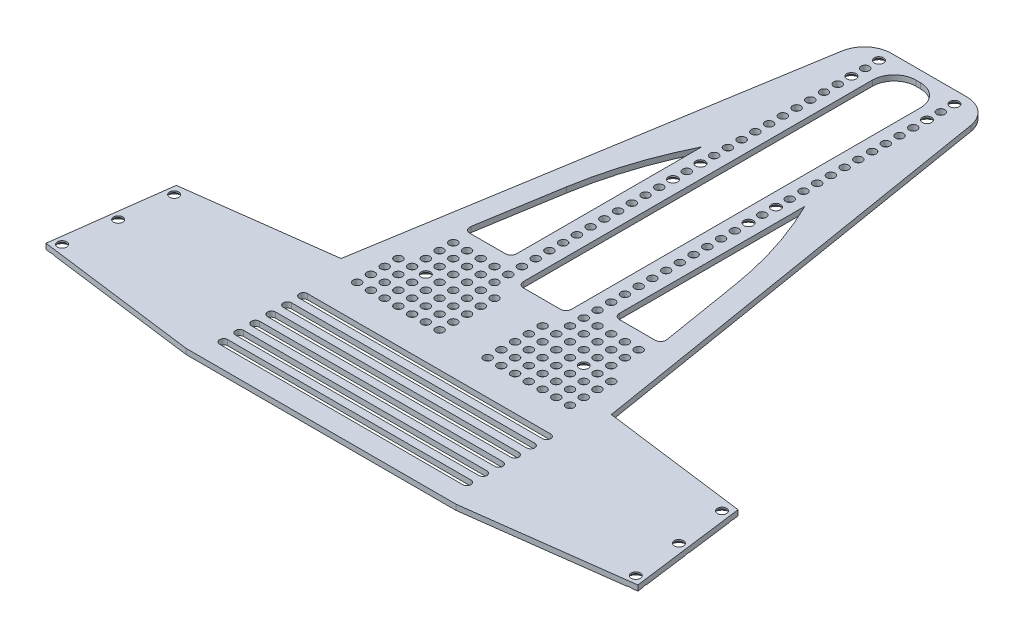
SolidWorks part; units mm, degrees
material "3003 합금"
ref_plane "정면" through (0, 0, 0) normal (0, 0, 1) x (1, 0, 0)
ref_plane "윗면" through (0, 0, 0) normal (0, 1, 0) x (1, 0, 0)
ref_plane "우측면" through (0, 0, 0) normal (1, 0, 0) x (0, 0, -1)
sketch "스케치1" plane through (0, 0, 0) normal (0, 1, 0) x (1, 0, 0)
  line L0 (-13.97, 75) -> (13.97, 75)
  line L1 (-150, -150) -> (150, -150) construction
  line L2 (-150, -150) -> (-150, 150) construction
  line L3 (-150, 150) -> (150, 150) construction
  line L4 (150, -150) -> (150, 150) construction
  line L5 (-0.8906, 70.9664) -> (0.8894, 70.9664)
  line L6 (0, 5.5338) -> (0, -144.4662) construction
  line L7 (-109.4949, -142.2307) -> (-50, -150)
  line L8 (36.2635, -58.3028) -> (31.2555, -27.834)
  line L9 (-103.9269, -99.5927) -> (-50, -92.5506)
  line L10 (-103.9269, -99.5927) -> (-109.4949, -142.2307)
  line L11 (-50, -150) -> (50, -150)
  line L12 (-50, -92.5506) -> (-23.8376, 66.6219)
  line L13 (103.9269, -99.5927) -> (109.4949, -142.2307)
  line L14 (109.4949, -142.2307) -> (50, -150)
  line L15 (-19.05, 10) -> (-19.05, -58.6272)
  line L16 (-45.0184, -136.6) -> (44.9816, -136.6)
  line L17 (103.9269, -99.5927) -> (50, -92.5506)
  line L18 (-8.89, 62.9664) -> (-8.89, -66.24)
  line L19 (-6.89, -68.24) -> (6.89, -68.24)
  line L20 (8.89, 62.9664) -> (8.89, -66.24)
  line L21 (-45.0184, -142.5) -> (44.9816, -142.5)
  line L22 (-44.9816, -133.6) -> (45.0184, -133.6)
  line L23 (-44.9816, -139.5) -> (45.0184, -139.5)
  line L24 (-45.0184, -136.6) -> (45.0184, -133.6) construction
  line L25 (-13.97, 70.42) -> (-13.97, -50.8622) construction
  line L26 (-101.3406, -102.956) -> (-106.1317, -139.6444) construction
  line L27 (-45.0184, -142.5) -> (45.0184, -139.5) construction
  line L28 (13.97, 70.42) -> (13.97, -50.9078) construction
  line L29 (-44.9816, -139.5) -> (44.9816, -142.5) construction
  line L30 (50, -92.5506) -> (23.8376, 66.6219)
  line L31 (-13.97, -92.14) -> (-13.97, -97.22) construction
  line L32 (-44.9816, -133.6) -> (44.9816, -136.6) construction
  line L33 (-45.0184, -130.7) -> (44.9816, -130.7)
  line L34 (-44.9816, -127.7) -> (45.0184, -127.7)
  line L35 (-45.0184, -130.7) -> (45.0184, -127.7) construction
  line L36 (-44.9816, -127.7) -> (44.9816, -130.7) construction
  line L37 (-45.0184, -124.8) -> (44.9816, -124.8)
  line L38 (-44.9816, -121.8) -> (45.0184, -121.8)
  line L39 (-45.0184, -124.8) -> (45.0184, -121.8) construction
  line L40 (-44.9816, -121.8) -> (44.9816, -124.8) construction
  line L41 (-45.0184, -118.9) -> (44.9816, -118.9)
  line L42 (-44.9816, -115.9) -> (45.0184, -115.9)
  line L43 (-45.0184, -118.9) -> (45.0184, -115.9) construction
  line L44 (-44.9816, -115.9) -> (44.9816, -118.9) construction
  line L45 (-45.0184, -113) -> (44.9816, -113)
  line L46 (-44.9816, -110) -> (45.0184, -110)
  line L47 (-45.0184, -113) -> (45.0184, -110) construction
  line L48 (-44.9816, -110) -> (44.9816, -113) construction
  line L49 (-36.2635, -58.3028) -> (-31.2555, -27.834)
  line L50 (-34.29, -60.6272) -> (-21.05, -60.6272)
  line L51 (13.97, -92.14) -> (13.97, -97.22) construction
  line L52 (19.05, 10) -> (19.05, -58.6272)
  line L53 (-103.9269, -99.5927) -> (-94.9739, -100.7619) construction
  line L58 (34.29, -60.6272) -> (21.05, -60.6272)
  line L63 (-45.0184, -107.1) -> (44.9816, -107.1) [skipped]
  line L64 (-44.9816, -104.1) -> (45.0184, -104.1) [skipped]
  line L65 (-45.0184, -107.1) -> (45.0184, -104.1) construction
  line L66 (-44.9816, -104.1) -> (44.9816, -107.1) construction
  line L67 (-44.9816, -98.2) -> (45.0184, -98.2) [skipped]
  line L68 (-45.0184, -101.2) -> (45.0184, -98.2) construction
  line L69 (-44.9816, -98.2) -> (44.9816, -101.2) construction
  line L70 (-45.0184, -101.2) -> (44.9816, -101.2) [skipped]
  circle A0 centre (-13.97, 65.34) radius 1.5
  circle A1 centre (-13.97, 60.26) radius 1.5
  circle A2 centre (-13.97, 70.42) radius 1.5
  circle A3 centre (-13.97, 55.18) radius 1.5
  arc A4 (13.97, 75) -> (23.8376, 66.6219) centre (13.97, 65) cw
  arc A5 (-13.97, 75) -> (-23.8376, 66.6219) centre (-13.97, 65) ccw
  circle A6 centre (-13.97, 50.1) radius 1.5
  circle A7 centre (-13.97, 45.02) radius 1.5
  circle A8 centre (-13.97, 39.94) radius 1.5
  circle A9 centre (-13.97, 34.86) radius 1.5
  circle A10 centre (-13.97, 29.78) radius 1.5
  circle A11 centre (-13.97, 24.7) radius 1.5
  circle A12 centre (-13.97, 19.62) radius 1.5
  circle A13 centre (-13.97, 14.54) radius 1.5
  circle A14 centre (-13.97, 9.46) radius 1.5
  circle A15 centre (-13.97, 4.38) radius 1.5
  circle A16 centre (-13.97, -0.7) radius 1.5
  circle A17 centre (-13.97, -5.78) radius 1.5
  circle A18 centre (-13.97, -10.86) radius 1.5
  circle A19 centre (-13.97, -15.94) radius 1.5
  circle A20 centre (-13.97, -21.02) radius 1.5
  circle A21 centre (-13.97, -26.1) radius 1.5
  circle A22 centre (-13.97, -31.18) radius 1.5
  circle A23 centre (-13.97, -36.26) radius 1.5
  circle A24 centre (-13.97, -41.34) radius 1.5
  circle A25 centre (-13.97, -46.42) radius 1.5
  circle A26 centre (-13.97, -51.5) radius 1.5
  circle A27 centre (-13.97, -56.58) radius 1.5
  circle A28 centre (-13.97, -61.66) radius 1.5
  circle A29 centre (-13.97, -66.74) radius 1.5
  circle A30 centre (-13.97, -71.82) radius 1.5
  circle A31 centre (-13.97, -76.9) radius 1.5
  circle A32 centre (-13.97, -81.98) radius 1.5
  circle A33 centre (-13.97, -87.06) radius 1.5
  circle A34 centre (-13.97, -92.14) radius 1.5
  circle A36 centre (-19.05, -66.74) radius 1.5
  circle A37 centre (-19.05, -71.82) radius 1.5
  circle A38 centre (-19.05, -76.9) radius 1.5
  circle A39 centre (-19.05, -81.98) radius 1.5
  circle A40 centre (-19.05, -87.06) radius 1.5
  circle A41 centre (101.3406, -102.956) radius 1.5
  circle A43 centre (-24.13, -66.74) radius 1.5
  circle A44 centre (-24.13, -71.82) radius 1.5
  circle A45 centre (-24.13, -76.9) radius 1.5
  circle A46 centre (-24.13, -81.98) radius 1.5
  circle A47 centre (-19.05, -92.14) radius 1.5
  circle A48 centre (103.7361, -121.3002) radius 1.5
  circle A50 centre (-29.21, -66.74) radius 1.5
  circle A51 centre (-29.21, -71.82) radius 1.5
  circle A52 centre (-29.21, -76.9) radius 1.5
  circle A53 centre (-29.21, -81.98) radius 1.5
  arc A54 (8.89, 62.9664) -> (0.8894, 70.9664) centre (0.89, 62.9664) ccw
  arc A55 (-8.89, 62.9664) -> (-0.8906, 70.9664) centre (-0.89, 62.9664) cw
  circle A56 centre (106.1317, -139.6444) radius 1.5
  circle A57 centre (-8.89, -76.9) radius 1.5
  circle A59 centre (-34.29, -66.74) radius 1.5
  circle A60 centre (-34.29, -71.82) radius 1.5
  circle A61 centre (-34.29, -76.9) radius 1.5
  circle A62 centre (-8.89, -81.98) radius 1.5
  circle A63 centre (-8.89, -87.06) radius 1.5
  circle A64 centre (-8.89, -92.14) radius 1.5
  circle A65 centre (-24.13, -87.06) radius 1.5
  circle A66 centre (-24.13, -92.14) radius 1.5
  circle A67 centre (-29.21, -87.06) radius 1.5
  circle A68 centre (-29.21, -92.14) radius 1.5
  circle A69 centre (-34.29, -87.06) radius 1.5
  circle A70 centre (13.97, 39.94) radius 1.5
  circle A71 centre (13.97, 45.02) radius 1.5
  circle A72 centre (13.97, 50.1) radius 1.5
  circle A73 centre (13.97, 55.18) radius 1.5
  circle A74 centre (13.97, 70.42) radius 1.5
  circle A75 centre (13.97, 60.26) radius 1.5
  circle A76 centre (13.97, 65.34) radius 1.5
  arc A77 (31.2555, -27.834) -> (19.05, 10) centre (-100.7312, -49.528) ccw
  circle A78 centre (13.97, -41.34) radius 1.5
  circle A79 centre (13.97, -36.26) radius 1.5
  circle A80 centre (13.97, -31.18) radius 1.5
  circle A81 centre (13.97, -26.1) radius 1.5
  circle A82 centre (13.97, -21.02) radius 1.5
  circle A83 centre (13.97, -15.94) radius 1.5
  circle A84 centre (13.97, -10.86) radius 1.5
  circle A85 centre (13.97, -5.78) radius 1.5
  circle A86 centre (13.97, -0.7) radius 1.5
  circle A87 centre (13.97, 4.38) radius 1.5
  arc A88 (-45.0184, -142.5) -> (-44.9816, -139.5) centre (-45, -141) cw
  arc A89 (44.9816, -142.5) -> (45.0184, -139.5) centre (45, -141) ccw
  arc A90 (-45.0184, -136.6) -> (-44.9816, -133.6) centre (-45, -135.1) cw
  arc A91 (44.9816, -136.6) -> (45.0184, -133.6) centre (45, -135.1) ccw
  arc A92 (-45.0184, -130.7) -> (-44.9816, -127.7) centre (-45, -129.2) cw
  arc A93 (44.9816, -130.7) -> (45.0184, -127.7) centre (45, -129.2) ccw
  arc A94 (-45.0184, -124.8) -> (-44.9816, -121.8) centre (-45, -123.3) cw
  arc A95 (44.9816, -124.8) -> (45.0184, -121.8) centre (45, -123.3) ccw
  circle A96 centre (-106.1317, -139.6444) radius 1.5
  circle A97 centre (-101.3406, -102.956) radius 1.5
  circle A98 centre (-103.7361, -121.3002) radius 1.5
  circle A99 centre (-34.29, -92.14) radius 1.5
  circle A100 centre (-39.37, -87.06) radius 1.5
  circle A101 centre (-39.37, -92.14) radius 1.5
  arc A102 (-45.0184, -118.9) -> (-44.9816, -115.9) centre (-45, -117.4) cw
  arc A103 (44.9816, -118.9) -> (45.0184, -115.9) centre (45, -117.4) ccw
  arc A104 (-45.0184, -113) -> (-44.9816, -110) centre (-45, -111.5) cw
  arc A105 (44.9816, -113) -> (45.0184, -110) centre (45, -111.5) ccw
  circle A106 centre (13.97, 9.46) radius 1.5
  circle A107 centre (13.97, 14.54) radius 1.5
  circle A108 centre (-39.37, -81.98) radius 1.5
  circle A109 centre (-13.97, -97.22) radius 1.5
  circle A110 centre (13.97, 19.62) radius 1.5
  circle A111 centre (13.97, 24.7) radius 1.5
  circle A112 centre (13.97, 29.78) radius 1.5
  circle A113 centre (13.97, 34.86) radius 1.5
  circle A114 centre (13.97, -66.74) radius 1.5
  circle A115 centre (34.29, -66.74) radius 1.5
  circle A116 centre (29.21, -66.74) radius 1.5
  circle A117 centre (24.13, -66.74) radius 1.5
  circle A118 centre (19.05, -66.74) radius 1.5
  arc A119 (19.05, -58.6272) -> (21.05, -60.6272) centre (21.05, -58.6272) ccw
  arc A120 (36.2635, -58.3028) -> (34.29, -60.6272) centre (34.29, -58.6272) cw
  circle A125 centre (13.97, -61.66) radius 1.5
  circle A126 centre (13.97, -56.58) radius 1.5
  circle A127 centre (13.97, -51.5) radius 1.5
  circle A128 centre (13.97, -46.42) radius 1.5
  circle A129 centre (-19.05, -97.22) radius 1.5
  circle A130 centre (-8.89, -97.22) radius 1.5
  circle A131 centre (-24.13, -97.22) radius 1.5
  circle A132 centre (-29.21, -97.22) radius 1.5
  circle A133 centre (-34.29, -97.22) radius 1.5
  circle A134 centre (8.89, -92.14) radius 1.5
  arc A135 (-45.0184, -107.1) -> (-44.9816, -104.1) centre (-45, -105.6) cw [skipped]
  arc A136 (44.9816, -107.1) -> (45.0184, -104.1) centre (45, -105.6) ccw [skipped]
  circle A137 centre (8.89, -87.06) radius 1.5
  arc A138 (-8.89, -66.24) -> (-6.89, -68.24) centre (-6.89, -66.24) ccw
  arc A139 (6.89, -68.24) -> (8.89, -66.24) centre (6.89, -66.24) ccw
  arc A140 (-31.2555, -27.834) -> (-19.05, 10) centre (100.7312, -49.528) cw
  arc A141 (-36.2635, -58.3028) -> (-34.29, -60.6272) centre (-34.29, -58.6272) ccw
  circle A142 centre (8.89, -81.98) radius 1.5
  circle A143 centre (34.29, -76.9) radius 1.5
  circle A144 centre (34.29, -71.82) radius 1.5
  circle A145 centre (8.89, -76.9) radius 1.5
  arc A146 (-19.05, -58.6272) -> (-21.05, -60.6272) centre (-21.05, -58.6272) cw
  circle A147 centre (-39.37, -97.22) radius 1.5
  circle A148 centre (8.89, -97.22) radius 1.5
  circle A149 centre (29.21, -76.9) radius 1.5
  circle A150 centre (29.21, -71.82) radius 1.5
  circle A151 centre (39.37, -81.98) radius 1.5
  circle A152 centre (39.37, -97.22) radius 1.5
  circle A153 centre (24.13, -81.98) radius 1.5
  circle A154 centre (24.13, -76.9) radius 1.5
  circle A155 centre (24.13, -71.82) radius 1.5
  circle A156 centre (34.29, -97.22) radius 1.5
  circle A157 centre (29.21, -97.22) radius 1.5
  circle A158 centre (19.05, -81.98) radius 1.5
  circle A159 centre (19.05, -76.9) radius 1.5
  circle A160 centre (19.05, -71.82) radius 1.5
  circle A161 centre (24.13, -97.22) radius 1.5
  circle A162 centre (19.05, -97.22) radius 1.5
  circle A163 centre (13.97, -81.98) radius 1.5
  circle A164 centre (13.97, -76.9) radius 1.5
  circle A165 centre (13.97, -71.82) radius 1.5
  circle A166 centre (13.97, -97.22) radius 1.5
  circle A167 centre (39.37, -92.14) radius 1.5
  circle A168 centre (-34.29, -81.98) radius 1.5
  circle A169 centre (39.37, -87.06) radius 1.5
  circle A170 centre (34.29, -92.14) radius 1.5
  circle A171 centre (34.29, -87.06) radius 1.5
  circle A172 centre (34.29, -81.98) radius 1.5
  circle A173 centre (29.21, -92.14) radius 1.5
  circle A174 centre (29.21, -87.06) radius 1.5
  circle A175 centre (29.21, -81.98) radius 1.5
  circle A176 centre (24.13, -92.14) radius 1.5
  circle A177 centre (24.13, -87.06) radius 1.5
  circle A178 centre (19.05, -92.14) radius 1.5
  circle A179 centre (19.05, -87.06) radius 1.5
  circle A180 centre (13.97, -92.14) radius 1.5
  circle A181 centre (13.97, -87.06) radius 1.5
  circle A185 centre (-34.29, -81.98) radius 1.5 [skipped]
  circle A190 centre (-29.21, -81.98) radius 1.5 [skipped]
  circle A191 centre (-8.89, -71.82) radius 1.5 [skipped]
  circle A192 centre (-3.81, -71.82) radius 1.5 [skipped]
  circle A193 centre (-3.81, -76.9) radius 1.5 [skipped]
  circle A194 centre (-3.81, -81.98) radius 1.5 [skipped]
  arc A201 (-45.0184, -101.2) -> (-44.9816, -98.2) centre (-45, -99.7) cw [skipped]
  arc A202 (44.9816, -101.2) -> (45.0184, -98.2) centre (45, -99.7) ccw [skipped]
  circle A203 centre (-13.97, -87.06) radius 1.5 [skipped]
  circle A204 centre (-13.97, -92.14) radius 1.5 [skipped]
  circle A205 centre (-19.05, -61.66) radius 1.5 [skipped]
  circle A206 centre (-24.13, -61.66) radius 1.5 [skipped]
  circle A207 centre (-29.21, -61.66) radius 1.5 [skipped]
  circle A208 centre (-34.29, -61.66) radius 1.5 [skipped]
  point P0 (0, 0)
  point P8 (0, -141)
  point P17 (0, 70)
  point P23 (-109.4949, -142.2307)
  point P24 (0, 75)
  point P133 (0, -150)
  point P145 (0, -99.7)
  point P215 (0, -105.6)
  point P217 (0, -135.1)
  point P224 (0, -129.2)
  point P241 (0, -123.3)
  point P248 (0, -117.4)
  point P255 (0, -111.5)
  dimension "D11" = 5.08
  dimension "D14" = 3
  dimension "D16" = 2
  dimension "D21" = 8
  dimension "D23" = 2
  dimension "D24" = 17.78
  dimension "D28" = 3
  dimension "D30" = 3
  dimension "D43" = 5.08
  dimension "D25" = 7
  dimension "D31" = 3
  dimension "D40" = 3
  dimension "D41" = 2
  dimension "D13" = 5.08
  dimension "D37" = 9
  dimension "D42" = 2
  dimension "D10" = 7.44
  dimension "D36" = 8
  dimension "D38" = 90
  dimension "D6" = 10
  dimension "D26" = 3
  dimension "D35" = 1.5001
  dimension "D7" = 50
  dimension "D19" = 5.08
  dimension "D56" = 150.7
  dimension "D60" = 2
  dimension "D61" = 17.78
  dimension "D20" = 3
  dimension "D29" = 1.5001
  dimension "D5" = 43
  dimension "D8" = 33
  dimension "D9" = 60
  dimension "D12" = 5
  dimension "D15" = 27.94
  dimension "D17" = 3
  dimension "D22" = 17.78
  dimension "D33" = 18.5
  dimension "D34" = 18.5
  dimension "D44" = 5.08
  dimension "D45" = 8
  dimension "D46" = 65
  dimension "D47" = 90
  dimension "D27" = 104.88
  dimension "D39" = 3
  dimension "D48" = 4.58
  dimension "D49" = 225
  dimension "D50" = 8.66
  dimension "D51" = 8.66
  dimension "D52" = 45
  dimension "D53" = 45
  dimension "D54" = 5.9
  dimension "D55" = 5.08
  dimension "D57" = 150
  dimension "D58" = 150
  dimension "D59" = 5.9
  dimension "D62" = 5.08
  dimension "D63" = 22.86
  dimension "D64" = 5.08
  dimension "D65" = 5.08
  dimension "D32" = 2
  dimension "D18" = 3
extrude "보스-돌출1" add sketch "스케치1" along normal blind 2
hole_wizard "M3 접시 머리 나사용 카운터싱크1" positions "3D스케치1" profile "스케치2" countersink size "M3" standard "ISO" end condition through all
sketch3d "3D스케치1"
  line L0 (13.97, 2, -70.42) -> (13.97, 0, -70.42) construction
  line L1 (-13.97, 2, -70.42) -> (-13.97, 0, -70.42) construction
  line L2 (101.3406, 2, 102.956) -> (101.3406, 0, 102.956) construction
  line L3 (103.7361, 2, 121.3002) -> (103.7361, 0, 121.3002) construction
  line L4 (106.1317, 2, 139.6444) -> (106.1317, 0, 139.6444) construction
  line L5 (-101.3406, 2, 102.956) -> (-101.3406, 0, 102.956) construction
  line L6 (-103.7361, 2, 121.3002) -> (-103.7361, 0, 121.3002) construction
  line L7 (-106.1317, 2, 139.6444) -> (-106.1317, 0, 139.6444) construction
  line L8 (-13.97, 2, -4.38) -> (-13.97, 0, -4.38) construction
  line L9 (13.97, 2, -4.38) -> (13.97, 0, -4.38) construction
  line L10 (-13.97, 2, -60.26) -> (-13.97, 0, -60.26) construction
  line L11 (13.97, 2, -60.26) -> (13.97, 0, -60.26) construction
  line L12 (-13.97, 2, 5.78) -> (-13.97, 0, 5.78) construction
  line L13 (13.97, 2, 5.78) -> (13.97, 0, 5.78) construction
  line L16 (-29.21, 2, 81.98) -> (-29.21, 0, 81.98) construction
  line L17 (29.21, 2, 81.98) -> (29.21, 0, 81.98) construction
  point P0 (13.97, 0, -70.42)
  point P4 (-13.97, 0, -70.42)
  point P8 (101.3406, 0, 102.956)
  point P12 (103.7361, 0, 121.3002)
  point P16 (106.1317, 0, 139.6444)
  point P20 (-101.3406, 0, 102.956)
  point P24 (-103.7361, 0, 121.3002)
  point P28 (-106.1317, 0, 139.6444)
  point P32 (-13.97, 0, -4.38)
  point P36 (13.97, 0, -4.38)
  point P40 (-13.97, 0, -60.26)
  point P44 (13.97, 0, -60.26)
  point P48 (-13.97, 0, 5.78)
  point P52 (13.97, 0, 5.78)
  point P72 (-29.21, 0, 81.98)
  point P76 (29.21, 0, 81.98)
sketch "스케치2" plane through (13.97, 0, -70.42) normal (1, 0, 0) x (0, 0, -1)
  line L0 (0, 0) -> (0, 2)
  line L1 (0, 2) -> (1.7, 2)
  line L2 (1.7, 2) -> (1.7, 1.45)
  line L3 (1.7, 1.45) -> (3.15, 0)
  line L5 (3.15, 0) -> (0, 0)
  line L6 (-1.7, 1.45) -> (-3.15, 0) construction
  line L11 (0, -6.35) -> (0, 107.95) construction
  dimension "관통 구멍 지름" = 3.4
  dimension "관통 구멍 깊이" = 2
  dimension "표면 카운터싱크 지름" = 6.3
  dimension "표면 카운터싱크 각도" = 90
